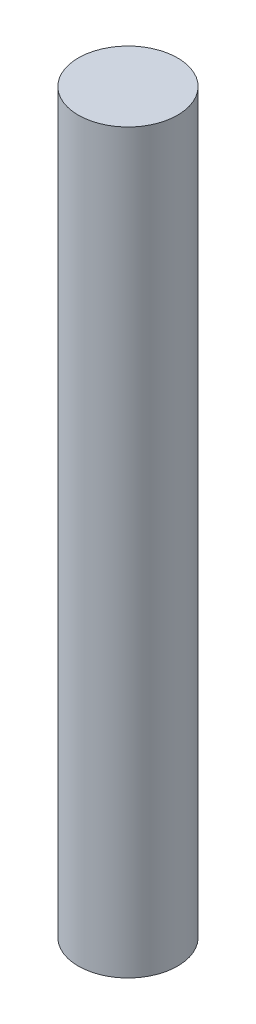
SolidWorks part; units mm, degrees
ref_plane "Front Plane" through (0, 0, 0) normal (0, 0, 1) x (1, 0, 0)
ref_plane "Top Plane" through (0, 0, 0) normal (0, 1, 0) x (1, 0, 0)
ref_plane "Right Plane" through (0, 0, 0) normal (1, 0, 0) x (0, 0, -1)
sketch "Sketch1" plane through (0, 0, 0) normal (0, 1, 0) x (1, 0, 0)
  circle A0 centre (0, 0) radius 27
  dimension "D1" = 54
extrude "Boss-Extrude1" add sketch "Sketch1" along normal blind 401
equation "\"Motor_Length\" = 401mm"
equation "\"Motor_OD\" = 54mm"
equation "\"D1@Sketch1\"=\"Motor_OD\""
equation "\"D1@Boss-Extrude1\"=\"Motor_Length\""
equation "\"Aft_Section_Length\" = 30in"
equation "\"Mid_Coupler_Length\" = 12in"
equation "\"AB_Coupler_OD_Length\"= 1in"
equation "\"AB_Coupling_Section_Length\"= 0.375in"
equation "\"AB_Coupler_Length\"= \"AB_Coupler_OD_Length\" + \"AB_Coupling_Section_Length\" * 2"
equation "\"Cutout_Angle\" = 60"
equation "\"AB_Paddle_Height\" = 0.375in"
equation "\"AB_Coupler_Num_Screws\"= 4"
equation "\"Num_Cutouts\" = 4"
equation "\"AB_Coupler_OD\"= 4.024in"
equation "\"AB_Coupler_ID\"= 3.7in"
equation "\"AB_Coupler_Surface_Diameter\"= 3.899in"
equation "\"AB_Coupling_Screw_Diameter\"= 0.1065in"
equation "\"AB_Central_Bushing_Length\" = 0.75in"
equation "\"Lead_Screw_Dist\" = 2in"
equation "\"Lead_Screw_Diam\" = 0.375in"
equation "\"Lead_Screw_Length\" = \"Mid_Coupler_Length\" + 2*0.375in + 2*0.5in"
equation "\"Paddle_Pin_Offset\" = 0.25in"
equation "\"Paddle_Pin_Radius\" = 2.25*2/3in"
equation "\"Paddle_Gear_OD\" = 3.2in"
equation "\"Fwd_BKHD_From_Top\" = 18in"
equation "\"Body_Tube_OD\"= 4.024in"
equation "\"Body_Tube_ID\"= 3.90in"
equation "\"Coupler_OD\" = 3.899in"
equation "\"Coupler_ID\" = 3.755in"
equation "\"Fwd_Section_Length\" = 25in"
equation "\"Mid_Section_Length\" = 6in"
equation "\"Aft_Upper_Tube_Length\" = 10in"
equation "\"Aft_Lower_Tube_Length\" = 18in"
equation "\"Nosecone_Coupler_Length\" = 5in"
equation "\"Avionics_Bulkhead_Thickness\" = 0.25in"
equation "\"Avionics_Bulkhead_Lip\" = 0.125in"
equation "\"Avionics_Board_Length\" = \"Mid_Coupler_Length\" - 2*\"Avionics_Bulkhead_Lip\""
equation "\"Lead_Screw_Hole_Diam\" = (27/64)*1in"
equation "\"Centering_Ring_Cutout_Dia\"=1.5in"
